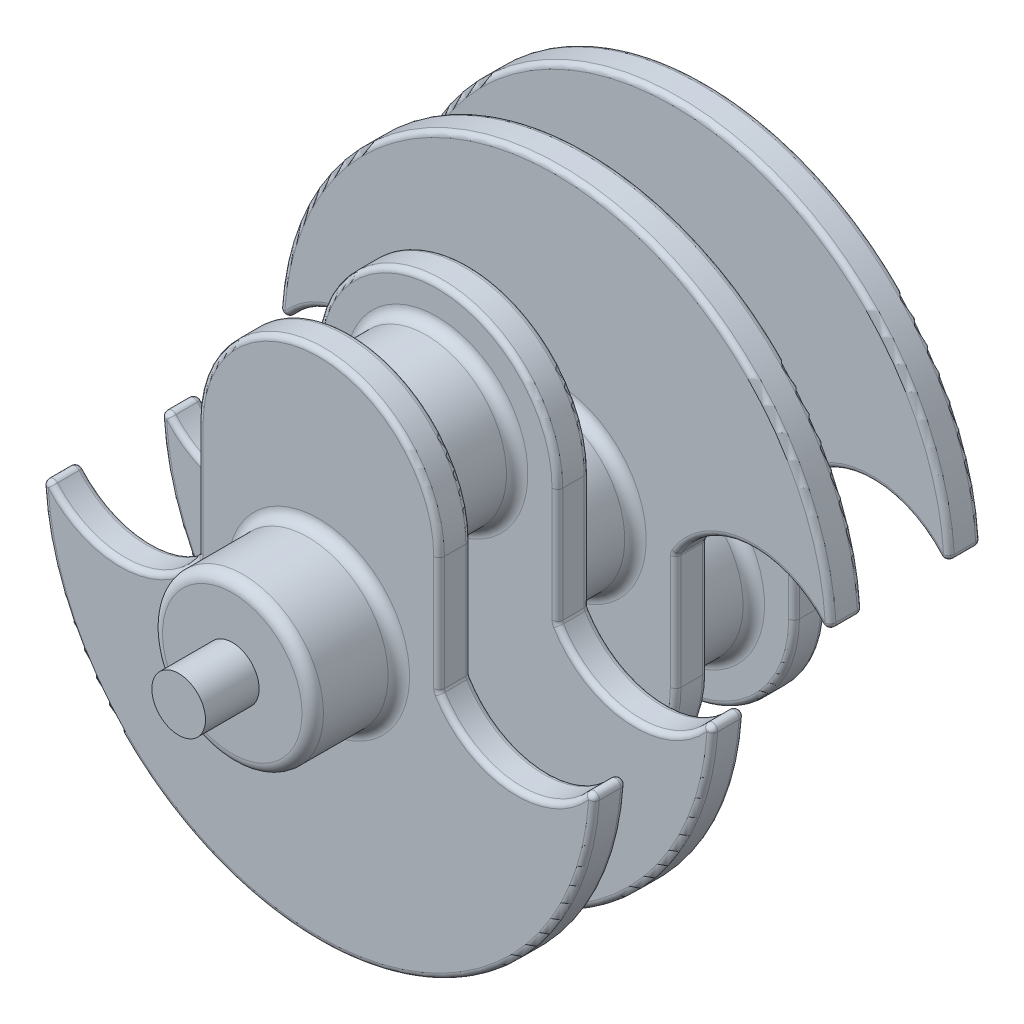
SolidWorks part; units mm, degrees
material "AISI 4340 Steel, normalized"
ref_plane "Front Plane" through (0, 0, 0) normal (0, 0, 1) x (1, 0, 0)
ref_plane "Top Plane" through (0, 0, 0) normal (0, 1, 0) x (1, 0, 0)
ref_plane "Right Plane" through (0, 0, 0) normal (1, 0, 0) x (0, 0, -1)
sketch "Sketch1" plane through (0, 0, 0) normal (0, 0, 1) x (1, 0, 0)
  circle A0 centre (0, 0) radius 30
  dimension "D1" = 30
extrude "Boss-Extrude1" add sketch "Sketch1" along normal blind 32.13
sketch "Sketch8" plane through (0, 0, 0) normal (0, 0, -1) x (-1, 0, 0)
  line L0 (-45, 43.2) -> (-45, 0)
  line L1 (45, 43.2) -> (45, 0)
  line L2 (-45, 0) -> (-89.1072, 0) construction
  arc A0 (45, 43.2) -> (-45, 43.2) centre (0, 43.2) ccw
  arc A5 (-103, 0) -> (103, 0) centre (0, 0) ccw
  arc A6 (-45, 0) -> (-103, 0) centre (-74, 16.8638) cw
  arc A7 (45, 0) -> (103, 0) centre (74, 16.8638) ccw
  dimension "D1" = 45
  dimension "D2" = 103
  dimension "D3" = 43.2
  dimension "D4" = 0
  dimension "D5" = 180
  dimension "D6" = 0
extrude "Boss-Extrude5" add sketch "Sketch8" along normal blind 12
sketch "Sketch2" plane through (0, 0, 32.13) normal (0, 0, 1) x (1, 0, 0)
  circle A0 centre (0, 0) radius 10
  dimension "D1" = 10
extrude "Boss-Extrude2" add sketch "Sketch2" along normal blind 20
sketch "Sketch9" plane through (0, 0, -12) normal (0, 0, -1) x (-1, 0, 0)
  circle A0 centre (0, 43.2) radius 30
  dimension "D2" = 30
  dimension "D1" = 43.2
extrude "Boss-Extrude6" add sketch "Sketch9" along normal blind 32.13
ref_plane "Plane4" through (0, 0, -88.26) normal (0, 0, -1) x (-1, 0, 0)
sketch "Sketch10" plane through (0, 0, -44.13) normal (0, 0, -1) x (-1, 0, 0)
  line L0 (-45, -43.2) -> (-45, 0)
  line L1 (45, -43.2) -> (45, 0)
  line L2 (45, 0) -> (85.967, 0) construction
  arc A0 (-45, -43.2) -> (45, -43.2) centre (0, -43.2) ccw
  arc A1 (-45, 0) -> (-103, 0) centre (-74, -16.8638) ccw
  arc A2 (45, 0) -> (103, 0) centre (74, -16.8638) cw
  arc A3 (-103, 0) -> (103, 0) centre (0, 0) cw
  dimension "D1" = 45
  dimension "D4" = 0
  dimension "D5" = 180
  dimension "D6" = 0
  dimension "D3" = 103
  dimension "D2" = 43.2
extrude "Boss-Extrude7" add sketch "Sketch10" along normal blind 12 from surface starting at plane "Plane4"
ref_plane "Plane3" through (0, 0, -132.39) normal (0, 0, -1) x (-1, 0, 0)
sketch "Sketch12" plane through (0, 0, -132.39) normal (0, 0, -1) x (-1, 0, 0)
  line L2 (45, -43.2) -> (45, 0)
  line L3 (45, -43.2) -> (45, 0)
  line L4 (-45, 0) -> (-45, -43.2)
  line L5 (-45, 0) -> (-45, -43.2)
  arc A12 (-45, -43.2) -> (45, -43.2) centre (0, -43.2) ccw
  arc A13 (103, 0) -> (45, 0) centre (74, -16.8638) ccw
  arc A14 (103, 0) -> (-103, 0) centre (0, 0) ccw
  arc A15 (-45, 0) -> (-103, 0) centre (-74, -16.8638) ccw
  arc A16 (-45, -43.2) -> (45, -43.2) centre (0, -43.2) ccw
  arc A17 (103, 0) -> (45, 0) centre (74, -16.8638) ccw
  arc A18 (103, 0) -> (-103, 0) centre (0, 0) ccw
  arc A19 (-45, 0) -> (-103, 0) centre (-74, -16.8638) ccw
  dimension "D1" = 0
extrude "Boss-Extrude8" add sketch "Sketch12" along normal blind 12
sketch "Sketch14" plane through (0, 0, -100.26) normal (0, 0, -1) x (-1, 0, 0)
  circle A0 centre (0, -43.2) radius 30
  dimension "D2" = 30
  dimension "D1" = 43.2
extrude "Boss-Extrude9" add sketch "Sketch14" along normal up to next
sketch "Sketch15" plane through (0, 0, -144.39) normal (0, 0, -1) x (-1, 0, 0)
  circle A1 centre (0, 0) radius 30
  circle A2 centre (0, 0) radius 30
  dimension "D1" = 0
extrude "Boss-Extrude10" add sketch "Sketch15" along normal blind 32.13
sketch "Sketch16" plane through (0, 0, -176.52) normal (0, 0, -1) x (-1, 0, 0)
  circle A1 centre (0, 0) radius 10
  circle A2 centre (0, 0) radius 10
  dimension "D1" = 0
extrude "Boss-Extrude11" add sketch "Sketch16" along normal blind 20
sketch "Sketch18" plane through (0, 0, -44.13) normal (0, 0, -1) x (-1, 0, 0)
  line L2 (-45, 43.2) -> (-45, 0)
  line L3 (-45, 43.2) -> (-45, 0)
  line L4 (45, 0) -> (45, 43.2)
  line L5 (45, 0) -> (45, 43.2)
  arc A4 (45, 43.2) -> (-45, 43.2) centre (0, 43.2) ccw
  arc A5 (-103, 0) -> (-45, 0) centre (-74, 16.8638) ccw
  arc A6 (-103, 0) -> (103, 0) centre (0, 0) ccw
  arc A7 (45, 0) -> (103, 0) centre (74, 16.8638) ccw
  arc A8 (45, 43.2) -> (-45, 43.2) centre (0, 43.2) ccw
  arc A9 (-103, 0) -> (-45, 0) centre (-74, 16.8638) ccw
  arc A10 (-103, 0) -> (103, 0) centre (0, 0) ccw
  arc A11 (45, 0) -> (103, 0) centre (74, 16.8638) ccw
  dimension "D1" = 0
extrude "Boss-Extrude12" add sketch "Sketch18" along normal blind 12
sketch "Sketch19" plane through (0, 0, -56.13) normal (0, 0, -1) x (-1, 0, 0)
  circle A1 centre (0, 0) radius 30
  circle A2 centre (0, 0) radius 30
  dimension "D1" = 0
extrude "Boss-Extrude13" add sketch "Sketch19" along normal up to next
fillet "Fillet1" radius 2 32 edges at (0, -103, -44.13) (-74, -16.683, -44.13) (-45, 21.6, -44.13) (45, 21.6, -44.13) (74, -16.683, -44.13) (0, -103, -56.13) (-74, -16.683, -56.13) (-45, 21.6, -56.13) (0, 88.2, -56.13) (45, 21.6, -56.13) (74, -16.683, -56.13) (103, 0, -50.13) (45, 0, -50.13) (-45, 0, -50.13) (-103, 0, -50.13) (0, 88.2, -44.13) (45, 21.6, 0) (74, -16.683, 0) (0, -103, 0) (-74, -16.683, 0) (-45, 21.6, 0) (0, 88.2, -12) (45, 21.6, -12) (74, -16.683, -12) (0, -103, -12) (-74, -16.683, -12) (-45, 21.6, -12) (-45, 0, -6) (-103, 0, -6) (103, 0, -6) (45, 0, -6) (0, 88.2, 0)
fillet "Fillet2" radius 2 16 edges at (0, 103, -132.39) (74, 16.683, -132.39) (45, -21.6, -132.39) (0, -88.2, -132.39) (-45, -21.6, -132.39) (-74, 16.683, -132.39) (74, 16.683, -144.39) (45, -21.6, -144.39) (0, -88.2, -144.39) (-45, -21.6, -144.39) (-74, 16.683, -144.39) (-103, 0, -138.39) (-45, 0, -138.39) (45, 0, -138.39) (103, 0, -138.39) (0, 103, -144.39)
fillet "Fillet3" radius 2 16 edges at (45, -21.6, -88.26) (74, 16.683, -88.26) (0, 103, -88.26) (-74, 16.683, -88.26) (-45, -21.6, -88.26) (0, -88.2, -88.26) (45, -21.6, -100.26) (74, 16.683, -100.26) (-74, 16.683, -100.26) (-45, -21.6, -100.26) (0, -88.2, -100.26) (45, 0, -94.26) (103, 0, -94.26) (-103, 0, -94.26) (-45, 0, -94.26) (0, 103, -100.26)
fillet "Fillet5" radius 4 2 edges at (30, 0, 32.13) (30, 0, 0)
fillet "Fillet6" radius 4 2 edges at (-30, 0, -144.39) (-30, 0, -176.52)
ref_plane "Plane5" through (0, 31.75, 0) normal (0, 1, 0) x (1, 0, 0)
sketch "Sketch20" plane through (0, 0, 0) normal (1, 0, 0) x (0, 0, -1)
  line L1 (100.26, -73.2) -> (100.26, -13.2)
  line L2 (100.26, -73.2) -> (100.26, -13.2)
  dimension "D1" = 0
ref_plane "Plane6" through (0, -73.2, 0) normal (0, 1, 0) x (1, 0, 0)
sketch "Sketch21" plane through (0, 31.75, 0) normal (0, 1, 0) x (1, 0, 0)
  line L2 (-30, 172.52) -> (30, 172.52) construction
  line L3 (-30, 172.52) -> (-30, 148.39) construction
  line L4 (-30, 148.39) -> (30, 148.39) construction
  line L5 (30, 172.52) -> (30, 148.39) construction
  circle A0 centre (0, 160.455) radius 2.5
  point P10 (0, 172.52)
  point P11 (30, 160.455)
  dimension "D1" = 5
sketch "Sketch27" plane through (0, 0, 0) normal (0, 0, 1) x (1, 0, 0)
  line L0 (0, 73.2) -> (0, -30) construction
  circle A1 centre (0, 43.2) radius 30
  circle A2 centre (0, 43.2) radius 30 construction
  circle A3 centre (0, 0) radius 30
  circle A4 centre (0, 0) radius 30 construction
  dimension "D1" = 0
  dimension "D2" = 0
ref_plane "Plane8" through (0, 73.2, 0) normal (0, -1, 0) x (-1, 0, 0)
ref_plane "Plane9" through (0, -30, 0) normal (0, -1, 0) x (-1, 0, 0)
sketch "Sketch28" plane through (0, -30, 0) normal (0, -1, 0) x (-1, 0, 0)
  line L1 (-30, -4) -> (30, -4) construction
  line L2 (-30, -4) -> (-30, -28.13) construction
  line L3 (-30, -28.13) -> (30, -28.13) construction
  line L4 (30, -4) -> (30, -28.13) construction
  line L5 (-30, -4) -> (30, -28.13) construction
  line L6 (-30, -28.13) -> (30, -4) construction
  circle A0 centre (0, -16.065) radius 2.5
  point P4 (0, -16.065)
  dimension "D1" = 5
sketch "Sketch29" plane through (0, 73.2, 0) normal (0, -1, 0) x (-1, 0, 0)
  line L1 (30, 44.13) -> (-30, 44.13) construction
  line L2 (30, 44.13) -> (30, 12) construction
  line L3 (30, 12) -> (-30, 12) construction
  line L4 (-30, 44.13) -> (-30, 12) construction
  line L5 (30, 44.13) -> (-30, 12) construction
  line L6 (30, 12) -> (-30, 44.13) construction
  circle A0 centre (0, 28.065) radius 2.5
  point P4 (0, 28.065)
sketch "Sketch31" plane through (0, 0, 0) normal (1, 0, 0) x (0, 0, -1)
  line L0 (20.0325, 73.2) -> (-16.065, -30) construction
  line L1 (44.13, 86.2) -> (44.13, 43.2) construction
  line L2 (12, 43.2) -> (12, 86.2) construction
  line L3 (44.13, 86.2) -> (44.13, 43.2) construction
  line L4 (12, 43.2) -> (12, 86.2) construction
  point P4 (0, 0)
  point P5 (0, 0)
  dimension "D1" = 8.0325
ref_plane "Plane10" through (0, 73.2, -28.065) normal (0, -0.9439, 0.3302) x (-1, 0, 0)
ref_plane "Plane11" through (0, -30, 16.065) normal (0, -0.9439, 0.3302) x (-1, 0, 0)
combine bodies "Combine1" operation type add bodies to combine 119 109 117
fillet "Fillet7" radius 4 6 edges at (-30, 43.2, -44.13) (-30, 43.2, -12) (-30, 0, -56.13) (-30, 0, -88.26) (-30, -43.2, -132.39) (-30, -43.2, -100.26)
sketch "Sketch39" plane through (0, -73.2, 0) normal (0, 1, 0) x (1, 0, 0)
  line L1 (30, 128.39) -> (-30, 128.39) construction
  line L2 (30, 128.39) -> (30, 104.26) construction
  line L3 (30, 104.26) -> (-30, 104.26) construction
  line L4 (-30, 128.39) -> (-30, 104.26) construction
  line L5 (30, 128.39) -> (-30, 104.26) construction
  line L6 (30, 104.26) -> (-30, 128.39) construction
  point P4 (0, 116.325)
sketch "Sketch40" plane through (0, 0, 0) normal (1, 0, 0) x (0, 0, -1)
  line L0 (160.455, 31.75) -> (124.3575, -73.2) construction
  line L1 (172.52, 31.75) -> (148.39, 31.75) construction
  line L3 (132.39, -43.2) -> (132.39, -86.2) construction
  point P4 (116.325, -73.2)
  point P5 (116.325, -73.2)
  point P6 (116.325, -73.2)
  point P9 (0, 0)
  dimension "D1" = 8.0325
ref_plane "Plane12" through (0, 31.75, -160.455) normal (0, -0.9456, 0.3252) x (-1, 0, 0)
ref_plane "Plane13" through (0, -73.2, -124.3575) normal (0, -0.9456, 0.3252) x (-1, 0, 0)
sketch "Sketch47" plane through (0, 73.2, -28.065) normal (0, -0.9439, 0.3302) x (-1, 0, 0)
  ellipse E0 centre (0, 0) end of major axis (2.5, 0) minor radius 2.3598 construction
  ellipse E1 centre (0, 0) end of major axis (2.5, 0) minor radius 2.3598
sketch "Sketch48" plane through (0, -30, 16.065) normal (0, -0.9439, 0.3302) x (-1, 0, 0)
  ellipse E0 centre (0, 0) end of major axis (2.5, 0) minor radius 2.3598 construction
  ellipse E1 centre (0, 0) end of major axis (2.5, 0) minor radius 2.3598
extrude "Cut-Extrude2" cut sketch "Sketch48" against normal through all
sketch "Sketch49" plane through (0, -73.2, -124.3575) normal (0, -0.9456, 0.3252) x (-1, 0, 0)
  circle A0 centre (0, 0) radius 2.5
  point P3 (0.5985, 1.3865)
  point P4 (0, 0)
  dimension "D1" = 5
extrude "Cut-Extrude3" cut sketch "Sketch49" against normal through all
sketch "Sketch50" plane through (0, 31.75, -160.455) normal (0, -0.9456, 0.3252) x (-1, 0, 0)
  circle A0 centre (0, 0) radius 2.5 construction
  circle A1 centre (0, 0) radius 2.5
extrude "Cut-Extrude4" cut sketch "Sketch50" along normal through all
sketch "Sketch51" plane through (0, 0, 0) normal (1, 0, 0) x (0, 0, -1)
  line L0 (20.0325, 73.2) -> (124.3575, -73.2) construction
ref_plane "Plane14" through (0, 73.2, -20.0325) normal (0, -0.8144, -0.5803) x (-1, 0, 0)
equation "\"CRR\"= 43.2mm'Crank Radius"
equation "\"D1@Sketch9\"=\"CRR\""
equation "\"D1@Sketch14\"=\"CRR\""
equation "\"JR\"= 30mm'Journal Radius"
equation "\"D1@Sketch1\"=\"JR\""
equation "\"D2@Sketch9\"=\"JR\""
equation "\"D2@Sketch14\"=\"JR\""
equation "\"LT\"= 12mm'Lobe Thickness"
equation "\"D1@Boss-Extrude5\"=\"LT\""
equation "\"D1@Boss-Extrude7\"=\"LT\""
equation "\"D1@Boss-Extrude8\"=\"LT\""
equation "\"D1@Boss-Extrude12\"=\"LT\""
equation "\"D3@Sketch8\"=\"CRR\""
equation "\"D2@Sketch10\"=\"CRR\""
equation "\"JL\"= 24.13 + 2 * ( \"JF\" )'Journal Length"
equation "\"D1@Boss-Extrude1\"=\"JL\""
equation "\"D1@Boss-Extrude6\"=\"JL\""
equation "\"D1@Boss-Extrude10\"=\"JL\""
equation "\"LHD\"= 5mm'Lubrication Hole Diameter"
equation "\"D1@Sketch29\"=\"LHD\""
equation "\"JF\"= 4mm'Internal Journal Fillets"
equation "\"D1@Fillet7\"=\"JF\""
equation "\"D1@Fillet6\"=\"JF\""
equation "\"LR\"= 45mm'Lobe radius"
equation "\"CWR\"= 103mm'Counterweight Radius"
equation "\"D1@Sketch8\"=\"LR\""
equation "\"D2@Sketch8\"=\"CWR\""
equation "\"D3@Sketch10\"=\"CWR\""
equation "\"D1@Sketch10\"=\"LR\""
equation "\"CWA\"= 3.14159rad'Counterweight Arc"
equation "\"CWS\"= 0rad'Counterweight Slope"
equation "\"CWH\"= 0mm'Counterweight Offset"
equation "\"D4@Sketch8\"=\"CWH\""
equation "\"D5@Sketch8\"=\"CWA\""
equation "\"D6@Sketch8\"=\"CWS\""
equation "\"D4@Sketch10\"=\"CWH\""
equation "\"D5@Sketch10\"=\"CWA\""
equation "\"D6@Sketch10\"=\"CWS\""
